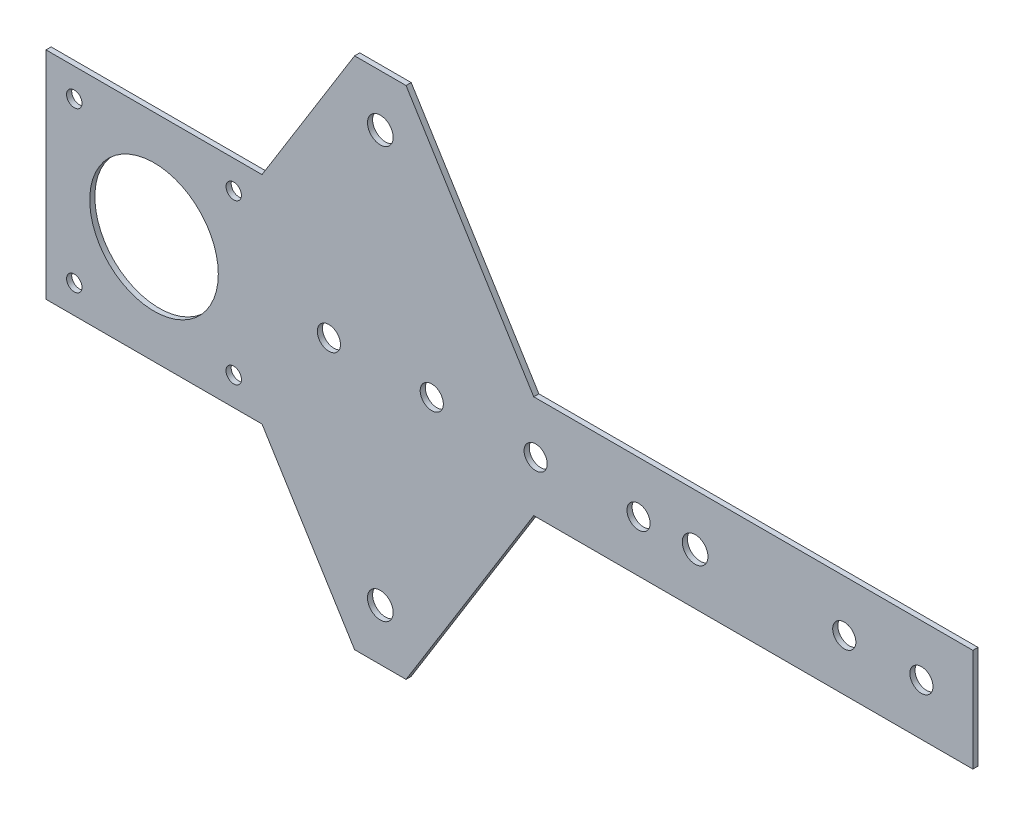
SolidWorks part; units mm, degrees
ref_plane "Front Plane" through (0, 0, 0) normal (0, 0, 1) x (1, 0, 0)
ref_plane "Top Plane" through (0, 0, 0) normal (0, 1, 0) x (1, 0, 0)
ref_plane "Right Plane" through (0, 0, 0) normal (1, 0, 0) x (0, 0, -1)
sketch "Sketch1" plane through (0, 0, 0) normal (0, 0, 1) x (1, 0, 0)
  line L0 (-90.1, 0) -> (90.1, 0) construction
  line L1 (-90.1, -21) -> (-48.1, -21)
  line L2 (-90.1, -21) -> (-90.1, 21)
  line L3 (-90.1, 21) -> (-48.1, 21)
  line L4 (90.1, -10) -> (90.1, 10)
  line L5 (-90.1, -21) -> (90.1, 21) construction
  line L6 (-90.1, 21) -> (90.1, -21) construction
  line L7 (-84.6, 15.5) -> (-69.1, 0) construction
  line L8 (-69.1, 0) -> (-84.6, 0) construction
  line L9 (-84.6, 0) -> (-84.6, 15.5) construction
  line L10 (-48.1, -21) -> (-30.1, -50)
  line L11 (-30.1, -50) -> (-20.1, -50)
  line L12 (-20.1, -50) -> (4.7276, -10)
  line L13 (4.7276, -10) -> (90.1, -10)
  line L14 (-20.1, 50) -> (4.7276, 10)
  line L15 (-30.1, 50) -> (-20.1, 50)
  line L16 (-48.1, 21) -> (-30.1, 50)
  line L17 (4.7276, 10) -> (90.1, 10)
  line L18 (-2.1, 21) -> (90.1, 21) construction
  line L19 (90.1, 10) -> (90.1, 21) construction
  line L20 (-2.1, -21) -> (90.1, -21) construction
  line L21 (90.1, -21) -> (90.1, -10) construction
  line L22 (-48.1, -21) -> (-2.1, -21) construction
  line L23 (-48.1, 21) -> (-2.1, 21) construction
  line L24 (-84.6, -15.5) -> (-90.1, -21) construction
  line L25 (-53.6, -15.5) -> (-48.1, -21) construction
  line L26 (-36.3069, -40) -> (-13.8931, -40) construction
  line L27 (-48.1, 21) -> (-48.1, -21) construction
  line L28 (-35.1, 0) -> (-25.1, -40) construction
  line L29 (-25.1, -40) -> (-15.1, 0) construction
  circle A26 centre (-69.1, 0) radius 12.5
  circle A27 centre (-84.6, 15.5) radius 1.5
  circle A31 centre (-25.1, -40) radius 2.5
  circle A32 centre (80.1, 0) radius 2.25
  circle A33 centre (65.1, 0) radius 2.25
  circle A34 centre (25.1, 0) radius 2.25
  circle A35 centre (5.1, 0) radius 2.25
  circle A36 centre (36.1, 0) radius 2.5
  circle A37 centre (-25.1, 40) radius 2.5
  circle A38 centre (-15.1, 0) radius 2.25
  circle A39 centre (-35.1, 0) radius 2.25
  circle A40 centre (-53.6, 15.5) radius 1.5
  circle A41 centre (-53.6, -15.5) radius 1.5
  circle A42 centre (-84.6, -15.5) radius 1.5
  point P0 (0, 0)
  point P21 (-69.1, 0)
  point P46 (-25.1, -50)
  point P55 (-69.1, 0)
  dimension "D3" = 25
  dimension "D4" = 65
  dimension "D5" = 5
  dimension "D9" = 40
  dimension "D10" = 20
  dimension "D11" = 4.5
  dimension "D12" = 61.2
  dimension "D13" = 54
  dimension "D15" = 10
  dimension "D16" = 10
  dimension "D17" = 42
  dimension "D19" = 5.5
  dimension "D21" = 42
  dimension "D1" = 3
  dimension "D20" = 4
  dimension "D2" = 15.5
  dimension "D6" = 40
  dimension "D7" = 10
  dimension "D14" = 20
  dimension "D18" = 20
  dimension "D8" = 15
base flange "Base-Flange1" sketch "Sketch1" thickness 1 reverse thickness direction no parameters "D1"=0.7366
sketch "Bend-Lines1" [suppressed] plane through (0, 0, 0) normal (0, 1, 0) x (1, 0, 0)
sketch "Bounding-Box1" [suppressed] plane through (0, 0, 0) normal (0, 1, 0) x (1, 0, 0)
sheet metal parameters "Sheet-Metal1" thickness 1 parameters "D1"=0.7366
flat pattern "Flat-Pattern1" [suppressed]
sketch "Bend-Lines2" plane through (0, 0, 0) normal (0, 1, 0) x (1, 0, 0)
sketch3d "Bounding-Box2" [suppressed]
  line L0 (-72.6501, -69.0744, 0) -> (96.5144, -7.6717, 0) construction
  line L1 (-105.8863, 22.4913, 0) -> (63.2782, 83.8941, 0) construction
  line L2 (-72.6501, -69.0744, 0) -> (-105.8863, 22.4913, 0) construction
  line L3 (96.5144, -7.6717, 0) -> (63.2782, 83.8941, 0) construction
